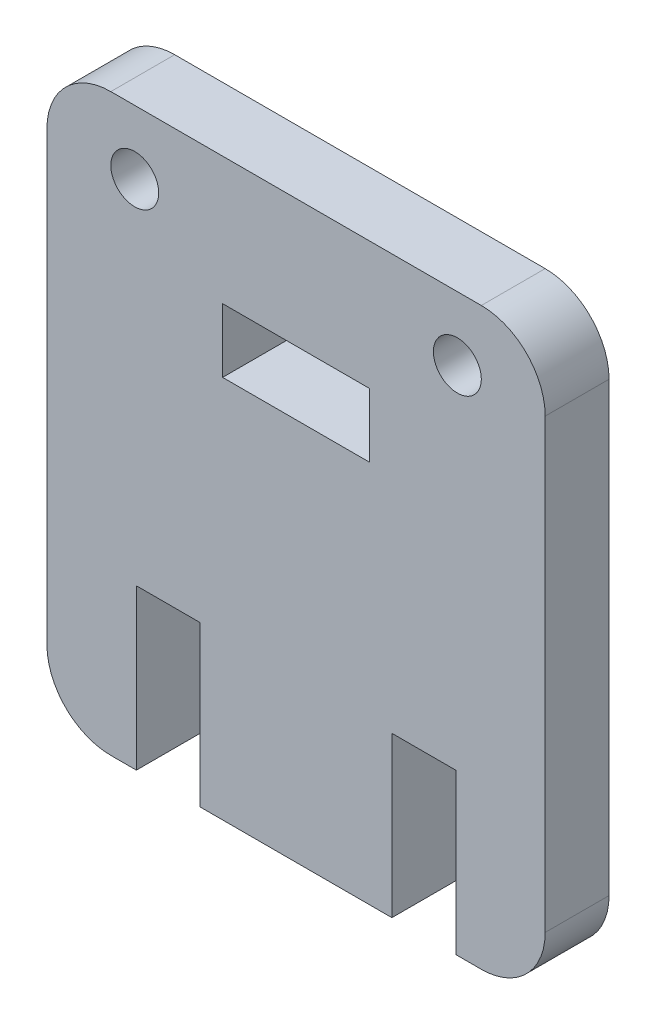
SolidWorks part; units mm, degrees
material "Acrylic (Medium-high impact)"
ref_plane "Front Plane" through (0, 0, 0) normal (0, 0, 1) x (1, 0, 0)
ref_plane "Top Plane" through (0, 0, 0) normal (0, 1, 0) x (1, 0, 0)
ref_plane "Right Plane" through (0, 0, 0) normal (1, 0, 0) x (0, 0, -1)
sketch "Model" plane through (0, 0, 0) normal (0, 0, 1) x (1, 0, 0)
  line L0 (2, 0) -> (2.8, 0)
  line L1 (2.8, 0) -> (2.8, 5)
  line L2 (2.8, 5) -> (4.8, 5)
  line L3 (4.8, 5) -> (4.8, 0)
  line L4 (4.8, 0) -> (10.8, 0)
  line L5 (10.8, 0) -> (10.8, 5)
  line L6 (10.8, 5) -> (12.8, 5)
  line L7 (12.8, 5) -> (12.8, 0)
  line L8 (12.8, 0) -> (13.6, 0)
  line L9 (0, 2) -> (0, 16)
  line L10 (2, 18) -> (13.6, 18)
  line L11 (15.6, 16) -> (15.6, 2)
  line L17 (5.5, 12) -> (10.1, 12)
  line L18 (10.1, 12) -> (10.1, 14)
  line L19 (10.1, 14) -> (5.5, 14)
  line L20 (5.5, 14) -> (5.5, 12)
  circle A0 centre (2.75, 16) radius 0.75
  circle A3 centre (12.85, 16) radius 0.75
  arc A4 (0, 16) -> (2, 18) centre (2, 16) cw
  arc A5 (2, 0) -> (0, 2) centre (2, 2) cw
  arc A6 (15.6, 2) -> (13.6, 0) centre (13.6, 2) cw
  arc A7 (13.6, 18) -> (15.6, 16) centre (13.6, 16) cw
  dimension "D1" = 1.5
  dimension "D2" = 2
  dimension "D3" = 15.6
  dimension "D4" = 13
  dimension "D5" = 6
  dimension "D6" = 2
  dimension "D10" = 5
  dimension "D13" = 2
other "AlignGroup1"
other "AlignGroup2"
other "AlignGroup3"
other "AlignGroup4"
other "AlignGroup5"
other "AlignGroup6"
other "AlignGroup7"
other "AlignGroup8"
extrude "Boss-Extrude1" add sketch "Model" along normal blind 2
